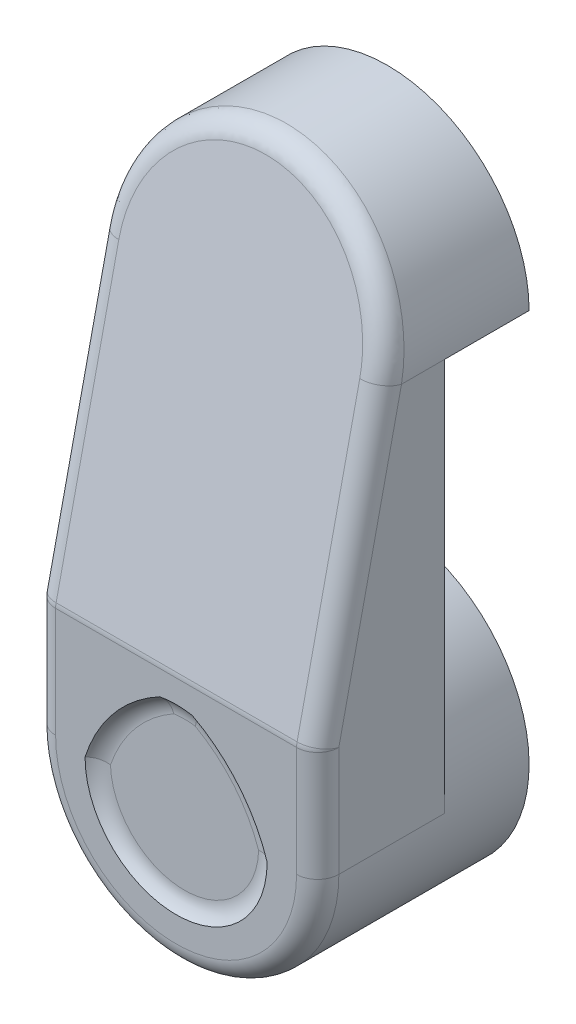
SolidWorks part; units mm, degrees
material "PET"
ref_plane "Front Plane" through (0, 0, 0) normal (0, 0, 1) x (1, 0, 0)
ref_plane "Top Plane" through (0, 0, 0) normal (0, 1, 0) x (1, 0, 0)
ref_plane "Right Plane" through (0, 0, 0) normal (1, 0, 0) x (0, 0, -1)
sketch "Sketch2" plane through (0, 0, 0) normal (0, 0, 1) x (1, 0, 0)
  line L0 (0, -4.65) -> (0, 4.65) construction
  line L1 (-3.35, -4.65) -> (-3.35, 4.65)
  line L2 (3.35, -4.65) -> (3.35, 4.65)
  arc A0 (-3.35, -4.65) -> (3.35, -4.65) centre (0, -4.65) ccw
  arc A1 (3.35, 4.65) -> (-3.35, 4.65) centre (0, 4.65) ccw
  point P2 (0, 0)
  dimension "D1" = 16
  dimension "D2" = 6.7
extrude "Boss-Extrude1" add sketch "Sketch2" against normal blind 5
fillet "Fillet1" radius 0.5 4 edges at (0, -8, 0) (-3.35, 0, 0) (0, 8, 0) (3.35, 0, 0)
sketch "Sketch4" plane through (0, 0, 0) normal (1, 0, 0) x (0, 0, -1)
  line L0 (5, 8) -> (2.2119, 8) construction
  line L1 (5, 8) -> (0.5, 8) construction
  line L2 (2.2119, 8) -> (0, -1.9946) construction
  line L3 (0, 4.65) -> (0, -4.65) construction
  line L4 (0, -1.9946) -> (0, -7.5) construction
  line L5 (2.2119, 8) -> (0.5, 8)
  line L6 (0, -1.9946) -> (0, 7.5)
  line L7 (0, 7.5) -> (0, 4.65) construction
  line L8 (2.2119, 8) -> (0, -1.9946)
  arc A0 (0.5, 8) -> (0, 7.5) centre (0.5, 7.5) ccw construction
  arc A1 (0, 7.5) -> (0.5, 8) centre (0.5, 7.5) cw
extrude "Cut-Extrude1" cut sketch "Sketch4" against normal through all both and the other way through all
sketch "Sketch5" plane through (0, 0, 0) normal (0, 0, 1) x (1, 0, 0)
  line L0 (0, -1.9946) -> (0, -7.5) construction
  line L1 (-2.85, -1.9946) -> (2.85, -1.9946) construction
  line L2 (0, -4.7473) -> (-1.3985, -4.7473) construction
  arc A0 (-2.85, -4.65) -> (2.85, -4.65) centre (0, -4.65) ccw construction
  arc A1 (-2.1539, -4.7473) -> (2.1539, -4.7473) centre (0, -4.7473) ccw
  arc A2 (-2.1539, -4.7473) -> (-0.3851, -2.6281) centre (1.3403, -5.866) cw
  arc A3 (2.1539, -4.7473) -> (0.3851, -2.6281) centre (-1.3403, -5.866) ccw
  arc A4 (0.3851, -2.6281) -> (-0.3851, -2.6281) centre (0, -4.7473) ccw
extrude "Cut-Extrude2" cut sketch "Sketch5" against normal blind 0.2
fillet "Fillet2" radius 0.5 4 edges at (0, -6.9012, -0.2) (0, -2.5934, -0.2) (-1.4764, -3.515, -0.2) (1.4764, -3.515, -0.2)
fillet "Fillet4" radius 0.5 6 edges at (3.35, 2.4573, -0.9853) (3.2036, -1.3329, -0.1464) (-3.2036, -1.3329, -0.1464) (-3.35, 2.4573, -0.9853) (0, -1.9946, 0) (0, 8, -2.2119)
sketch "Sketch7" plane through (0, 0, -5) normal (0, 0, -1) x (-1, 0, 0)
  line L0 (-2.85, 4.65) -> (-2.85, -4.65)
  line L1 (2.85, -4.65) -> (2.85, 4.65)
  line L2 (3.35, -4.65) -> (3.35, 4.65)
  line L3 (-3.35, 4.65) -> (-3.35, -4.65)
  line L4 (3.35, -4.65) -> (3.35, 4.65) construction
  line L5 (-3.35, 4.65) -> (-3.35, -4.65) construction
  arc A0 (-2.85, -4.65) -> (2.85, -4.65) centre (0, -4.65) ccw
  arc A1 (2.85, 4.65) -> (-2.85, 4.65) centre (0, 4.65) ccw
  arc A2 (-3.35, -4.65) -> (3.35, -4.65) centre (0, -4.65) ccw
  arc A3 (3.35, 4.65) -> (-3.35, 4.65) centre (0, 4.65) ccw
  arc A4 (-3.35, -4.65) -> (3.35, -4.65) centre (0, -4.65) ccw construction
  arc A5 (3.35, 4.65) -> (-3.35, 4.65) centre (0, 4.65) ccw construction
  dimension "D1" = 0
  dimension "D2" = 0.5
extrude "Cut-Extrude4" cut sketch "Sketch7" against normal blind 2
sketch "Sketch8" plane through (0, 0, 0) normal (1, 0, 0) x (0, 0, -1)
  line L0 (5, 4.65) -> (3, 4.65)
  line L1 (5, 4.65) -> (1.9826, 4.65) construction
  line L2 (3, 4.65) -> (3, -9.2418)
  line L3 (3, -9.2418) -> (5, -9.2418)
  line L4 (5, -9.2418) -> (5, 4.65)
  dimension "D1" = 2
extrude "Cut-Extrude5" cut sketch "Sketch8" against normal through all both and the other way through all
sketch "Sketch9" plane through (0, 0, -3) normal (0, 0, -1) x (-1, 0, 0)
  circle A0 centre (0, -4.65) radius 3.35
extrude "Boss-Extrude3" add sketch "Sketch9" along normal up to surface (2 mm away) up to face at (0, 6.2, -5)
sketch "Sketch10" plane through (0, 0, -3) normal (0, 0, -1) x (-1, 0, 0)
  line L1 (-0.25, -1.8992) -> (0.25, -1.8992)
  line L2 (-0.25, -1.8992) -> (-0.25, 7.6868)
  line L3 (-0.25, 7.6868) -> (0.25, 7.6868)
  line L4 (0.25, -1.8992) -> (0.25, 7.6868)
  dimension "D1" = 0.25
  dimension "D2" = 0.5
extrude "Boss-Extrude4" add sketch "Sketch10" along normal up to surface (2 mm away) up to face at (0, 6.2, -5)
sketch "Sketch11" plane through (0, 0, -5) normal (0, 0, -1) x (-1, 0, 0)
  circle A0 centre (0, -4.65) radius 1
  dimension "D1" = 2
extrude "Cut-Extrude6" cut sketch "Sketch11" against normal blind 0.5
sketch "Sketch12" plane through (0, 0, 0) normal (0, 0, 1) x (1, 0, 0)
  line L0 (0, -4.9644) -> (0, 10.3721) construction
